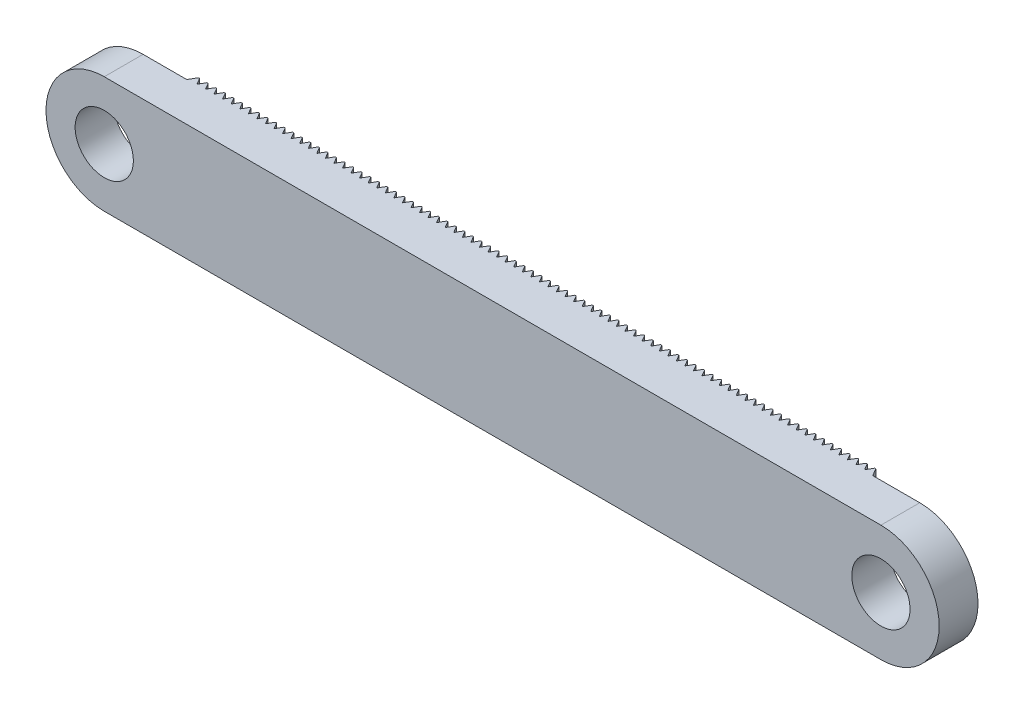
SolidWorks part; units mm, degrees
ref_plane "Front Plane" through (0, 0, 0) normal (0, 0, 1) x (1, 0, 0)
ref_plane "Top Plane" through (0, 0, 0) normal (0, 1, 0) x (1, 0, 0)
ref_plane "Right Plane" through (0, 0, 0) normal (1, 0, 0) x (0, 0, -1)
sketch "Sketch1" plane through (0, 0, 0) normal (0, 0, 1) x (1, 0, 0)
  line L0 (-20, 0) -> (20, 0) construction
  line L1 (-20, 3) -> (20, 3)
  line L2 (-20, -3) -> (20, -3)
  line L3 (0, 3) -> (0, -3) construction
  arc A0 (-20, 3) -> (-20, -3) centre (-20, 0) ccw
  arc A1 (20, -3) -> (20, 3) centre (20, 0) ccw
  circle A2 centre (-20, 0) radius 1.5
  circle A3 centre (20, 0) radius 1.5
  point P3 (0, 0)
  dimension "D1" = 3
  dimension "D2" = 40
  dimension "D3" = 6
extrude "Boss-Extrude1" add sketch "Sketch1" along normal blind 2
sketch "Sketch2" plane through (0, 0, 2) normal (0, 0, 1) x (1, 0, 0)
  circle A0 centre (0, 0) radius 1
  dimension "D1" = 2
extrude "Boss-Extrude2" [suppressed] add sketch "Sketch2" along normal blind 5
fillet "Fillet1" [suppressed] radius 0.25
sketch "Sketch5" plane through (0, 0, 0) normal (0, 1, 0) x (1, 0, 0)
  line L0 (-17.5306, 0.38) -> (-17.4694, 0.38)
  line L1 (-17.75, 0) -> (-17.5306, 0.38)
  line L2 (-17.4694, 0.38) -> (-17.25, 0)
  line L3 (20, 0) -> (-20, 0) construction
  line L4 (-17.25, 0) -> (-17.75, 0)
  line L5 (-17.3092, 0) -> (-17.0898, 0.38)
  line L6 (-17.0898, 0.38) -> (-17.0285, 0.38)
  line L7 (-17.0285, 0.38) -> (-16.8092, 0)
  line L8 (-16.8092, 0) -> (-17.3092, 0)
  line L9 (-16.8683, 0) -> (-16.6489, 0.38)
  line L10 (-16.6489, 0.38) -> (-16.5877, 0.38)
  line L11 (-16.5877, 0.38) -> (-16.3683, 0)
  line L12 (-16.3683, 0) -> (-16.8683, 0)
  line L13 (-16.4275, 0) -> (-16.2081, 0.38)
  line L14 (-16.2081, 0.38) -> (-16.1469, 0.38)
  line L15 (-16.1469, 0.38) -> (-15.9275, 0)
  line L16 (-15.9275, 0) -> (-16.4275, 0)
  line L17 (-15.9866, 0) -> (-15.7672, 0.38)
  line L18 (-15.7672, 0.38) -> (-15.706, 0.38)
  line L19 (-15.706, 0.38) -> (-15.4866, 0)
  line L20 (-15.4866, 0) -> (-15.9866, 0)
  line L21 (-15.5458, 0) -> (-15.3264, 0.38)
  line L22 (-15.3264, 0.38) -> (-15.2652, 0.38)
  line L23 (-15.2652, 0.38) -> (-15.0458, 0)
  line L24 (-15.0458, 0) -> (-15.5458, 0)
  line L25 (-15.1049, 0) -> (-14.8855, 0.38)
  line L26 (-14.8855, 0.38) -> (-14.8243, 0.38)
  line L27 (-14.8243, 0.38) -> (-14.6049, 0)
  line L28 (-14.6049, 0) -> (-15.1049, 0)
  line L29 (-14.6641, 0) -> (-14.4447, 0.38)
  line L30 (-14.4447, 0.38) -> (-14.3835, 0.38)
  line L31 (-14.3835, 0.38) -> (-14.1641, 0)
  line L32 (-14.1641, 0) -> (-14.6641, 0)
  line L33 (-14.2232, 0) -> (-14.0038, 0.38)
  line L34 (-14.0038, 0.38) -> (-13.9426, 0.38)
  line L35 (-13.9426, 0.38) -> (-13.7232, 0)
  line L36 (-13.7232, 0) -> (-14.2232, 0)
  line L37 (-13.7824, 0) -> (-13.563, 0.38)
  line L38 (-13.563, 0.38) -> (-13.5018, 0.38)
  line L39 (-13.5018, 0.38) -> (-13.2824, 0)
  line L40 (-13.2824, 0) -> (-13.7824, 0)
  line L41 (-13.3416, 0) -> (-13.1222, 0.38)
  line L42 (-13.1222, 0.38) -> (-13.0609, 0.38)
  line L43 (-13.0609, 0.38) -> (-12.8416, 0)
  line L44 (-12.8416, 0) -> (-13.3416, 0)
  line L45 (-12.9007, 0) -> (-12.6813, 0.38)
  line L46 (-12.6813, 0.38) -> (-12.6201, 0.38)
  line L47 (-12.6201, 0.38) -> (-12.4007, 0)
  line L48 (-12.4007, 0) -> (-12.9007, 0)
  line L49 (-12.4599, 0) -> (-12.2405, 0.38)
  line L50 (-12.2405, 0.38) -> (-12.1793, 0.38)
  line L51 (-12.1793, 0.38) -> (-11.9599, 0)
  line L52 (-11.9599, 0) -> (-12.4599, 0)
  line L53 (-12.019, 0) -> (-11.7996, 0.38)
  line L54 (-11.7996, 0.38) -> (-11.7384, 0.38)
  line L55 (-11.7384, 0.38) -> (-11.519, 0)
  line L56 (-11.519, 0) -> (-12.019, 0)
  line L57 (-11.5782, 0) -> (-11.3588, 0.38)
  line L58 (-11.3588, 0.38) -> (-11.2976, 0.38)
  line L59 (-11.2976, 0.38) -> (-11.0782, 0)
  line L60 (-11.0782, 0) -> (-11.5782, 0)
  line L61 (-11.1373, 0) -> (-10.9179, 0.38)
  line L62 (-10.9179, 0.38) -> (-10.8567, 0.38)
  line L63 (-10.8567, 0.38) -> (-10.6373, 0)
  line L64 (-10.6373, 0) -> (-11.1373, 0)
  line L65 (-10.6965, 0) -> (-10.4771, 0.38)
  line L66 (-10.4771, 0.38) -> (-10.4159, 0.38)
  line L67 (-10.4159, 0.38) -> (-10.1965, 0)
  line L68 (-10.1965, 0) -> (-10.6965, 0)
  line L69 (-10.2556, 0) -> (-10.0362, 0.38)
  line L70 (-10.0362, 0.38) -> (-9.975, 0.38)
  line L71 (-9.975, 0.38) -> (-9.7556, 0)
  line L72 (-9.7556, 0) -> (-10.2556, 0)
  line L73 (-9.8148, 0) -> (-9.5954, 0.38)
  line L74 (-9.5954, 0.38) -> (-9.5342, 0.38)
  line L75 (-9.5342, 0.38) -> (-9.3148, 0)
  line L76 (-9.3148, 0) -> (-9.8148, 0)
  line L77 (-9.374, 0) -> (-9.1546, 0.38)
  line L78 (-9.1546, 0.38) -> (-9.0933, 0.38)
  line L79 (-9.0933, 0.38) -> (-8.874, 0)
  line L80 (-8.874, 0) -> (-9.374, 0)
  line L81 (-8.9331, 0) -> (-8.7137, 0.38)
  line L82 (-8.7137, 0.38) -> (-8.6525, 0.38)
  line L83 (-8.6525, 0.38) -> (-8.4331, 0)
  line L84 (-8.4331, 0) -> (-8.9331, 0)
  line L85 (-8.4923, 0) -> (-8.2729, 0.38)
  line L86 (-8.2729, 0.38) -> (-8.2117, 0.38)
  line L87 (-8.2117, 0.38) -> (-7.9923, 0)
  line L88 (-7.9923, 0) -> (-8.4923, 0)
  line L89 (-8.0514, 0) -> (-7.832, 0.38)
  line L90 (-7.832, 0.38) -> (-7.7708, 0.38)
  line L91 (-7.7708, 0.38) -> (-7.5514, 0)
  line L92 (-7.5514, 0) -> (-8.0514, 0)
  line L93 (-7.6106, 0) -> (-7.3912, 0.38)
  line L94 (-7.3912, 0.38) -> (-7.33, 0.38)
  line L95 (-7.33, 0.38) -> (-7.1106, 0)
  line L96 (-7.1106, 0) -> (-7.6106, 0)
  line L97 (-7.1697, 0) -> (-6.9503, 0.38)
  line L98 (-6.9503, 0.38) -> (-6.8891, 0.38)
  line L99 (-6.8891, 0.38) -> (-6.6697, 0)
  line L100 (-6.6697, 0) -> (-7.1697, 0)
  line L101 (-6.7289, 0) -> (-6.5095, 0.38)
  line L102 (-6.5095, 0.38) -> (-6.4483, 0.38)
  line L103 (-6.4483, 0.38) -> (-6.2289, 0)
  line L104 (-6.2289, 0) -> (-6.7289, 0)
  line L105 (-6.288, 0) -> (-6.0686, 0.38)
  line L106 (-6.0686, 0.38) -> (-6.0074, 0.38)
  line L107 (-6.0074, 0.38) -> (-5.788, 0)
  line L108 (-5.788, 0) -> (-6.288, 0)
  line L109 (-5.8472, 0) -> (-5.6278, 0.38)
  line L110 (-5.6278, 0.38) -> (-5.5666, 0.38)
  line L111 (-5.5666, 0.38) -> (-5.3472, 0)
  line L112 (-5.3472, 0) -> (-5.8472, 0)
  line L113 (-5.4063, 0) -> (-5.187, 0.38)
  line L114 (-5.187, 0.38) -> (-5.1257, 0.38)
  line L115 (-5.1257, 0.38) -> (-4.9063, 0)
  line L116 (-4.9063, 0) -> (-5.4063, 0)
  line L117 (-4.9655, 0) -> (-4.7461, 0.38)
  line L118 (-4.7461, 0.38) -> (-4.6849, 0.38)
  line L119 (-4.6849, 0.38) -> (-4.4655, 0)
  line L120 (-4.4655, 0) -> (-4.9655, 0)
  line L121 (-4.5247, 0) -> (-4.3053, 0.38)
  line L122 (-4.3053, 0.38) -> (-4.2441, 0.38)
  line L123 (-4.2441, 0.38) -> (-4.0247, 0)
  line L124 (-4.0247, 0) -> (-4.5247, 0)
  line L125 (-4.0838, 0) -> (-3.8644, 0.38)
  line L126 (-3.8644, 0.38) -> (-3.8032, 0.38)
  line L127 (-3.8032, 0.38) -> (-3.5838, 0)
  line L128 (-3.5838, 0) -> (-4.0838, 0)
  line L129 (-3.643, 0) -> (-3.4236, 0.38)
  line L130 (-3.4236, 0.38) -> (-3.3624, 0.38)
  line L131 (-3.3624, 0.38) -> (-3.143, 0)
  line L132 (-3.143, 0) -> (-3.643, 0)
  line L133 (-3.2021, 0) -> (-2.9827, 0.38)
  line L134 (-2.9827, 0.38) -> (-2.9215, 0.38)
  line L135 (-2.9215, 0.38) -> (-2.7021, 0)
  line L136 (-2.7021, 0) -> (-3.2021, 0)
  line L137 (-2.7613, 0) -> (-2.5419, 0.38)
  line L138 (-2.5419, 0.38) -> (-2.4807, 0.38)
  line L139 (-2.4807, 0.38) -> (-2.2613, 0)
  line L140 (-2.2613, 0) -> (-2.7613, 0)
  line L141 (-2.3204, 0) -> (-2.101, 0.38)
  line L142 (-2.101, 0.38) -> (-2.0398, 0.38)
  line L143 (-2.0398, 0.38) -> (-1.8204, 0)
  line L144 (-1.8204, 0) -> (-2.3204, 0)
  line L145 (-1.8796, 0) -> (-1.6602, 0.38)
  line L146 (-1.6602, 0.38) -> (-1.599, 0.38)
  line L147 (-1.599, 0.38) -> (-1.3796, 0)
  line L148 (-1.3796, 0) -> (-1.8796, 0)
  line L149 (-1.4387, 0) -> (-1.2194, 0.38)
  line L150 (-1.2194, 0.38) -> (-1.1581, 0.38)
  line L151 (-1.1581, 0.38) -> (-0.9387, 0)
  line L152 (-0.9387, 0) -> (-1.4387, 0)
  line L153 (-0.9979, 0) -> (-0.7785, 0.38)
  line L154 (-0.7785, 0.38) -> (-0.7173, 0.38)
  line L155 (-0.7173, 0.38) -> (-0.4979, 0)
  line L156 (-0.4979, 0) -> (-0.9979, 0)
  line L157 (-0.5571, 0) -> (-0.3377, 0.38)
  line L158 (-0.3377, 0.38) -> (-0.2765, 0.38)
  line L159 (-0.2765, 0.38) -> (-0.0571, 0)
  line L160 (-0.0571, 0) -> (-0.5571, 0)
  line L161 (-0.1162, 0) -> (0.1032, 0.38)
  line L162 (0.1032, 0.38) -> (0.1644, 0.38)
  line L163 (0.1644, 0.38) -> (0.3838, 0)
  line L164 (0.3838, 0) -> (-0.1162, 0)
  line L165 (0.3246, 0) -> (0.544, 0.38)
  line L166 (0.544, 0.38) -> (0.6052, 0.38)
  line L167 (0.6052, 0.38) -> (0.8246, 0)
  line L168 (0.8246, 0) -> (0.3246, 0)
  line L169 (0.7655, 0) -> (0.9849, 0.38)
  line L170 (0.9849, 0.38) -> (1.0461, 0.38)
  line L171 (1.0461, 0.38) -> (1.2655, 0)
  line L172 (1.2655, 0) -> (0.7655, 0)
  line L173 (1.2063, 0) -> (1.4257, 0.38)
  line L174 (1.4257, 0.38) -> (1.4869, 0.38)
  line L175 (1.4869, 0.38) -> (1.7063, 0)
  line L176 (1.7063, 0) -> (1.2063, 0)
  line L177 (1.6472, 0) -> (1.8666, 0.38)
  line L178 (1.8666, 0.38) -> (1.9278, 0.38)
  line L179 (1.9278, 0.38) -> (2.1472, 0)
  line L180 (2.1472, 0) -> (1.6472, 0)
  line L181 (2.088, 0) -> (2.3074, 0.38)
  line L182 (2.3074, 0.38) -> (2.3686, 0.38)
  line L183 (2.3686, 0.38) -> (2.588, 0)
  line L184 (2.588, 0) -> (2.088, 0)
  line L185 (2.5289, 0) -> (2.7482, 0.38)
  line L186 (2.7482, 0.38) -> (2.8095, 0.38)
  line L187 (2.8095, 0.38) -> (3.0289, 0)
  line L188 (3.0289, 0) -> (2.5289, 0)
  line L189 (2.9697, 0) -> (3.1891, 0.38)
  line L190 (3.1891, 0.38) -> (3.2503, 0.38)
  line L191 (3.2503, 0.38) -> (3.4697, 0)
  line L192 (3.4697, 0) -> (2.9697, 0)
  line L193 (3.4105, 0) -> (3.6299, 0.38)
  line L194 (3.6299, 0.38) -> (3.6912, 0.38)
  line L195 (3.6912, 0.38) -> (3.9105, 0)
  line L196 (3.9105, 0) -> (3.4105, 0)
  line L197 (3.8514, 0) -> (4.0708, 0.38)
  line L198 (4.0708, 0.38) -> (4.132, 0.38)
  line L199 (4.132, 0.38) -> (4.3514, 0)
  line L200 (4.3514, 0) -> (3.8514, 0)
  line L201 (4.2922, 0) -> (4.5116, 0.38)
  line L202 (4.5116, 0.38) -> (4.5728, 0.38)
  line L203 (4.5728, 0.38) -> (4.7922, 0)
  line L204 (4.7922, 0) -> (4.2922, 0)
  line L205 (4.7331, 0) -> (4.9525, 0.38)
  line L206 (4.9525, 0.38) -> (5.0137, 0.38)
  line L207 (5.0137, 0.38) -> (5.2331, 0)
  line L208 (5.2331, 0) -> (4.7331, 0)
  line L209 (5.1739, 0) -> (5.3933, 0.38)
  line L210 (5.3933, 0.38) -> (5.4545, 0.38)
  line L211 (5.4545, 0.38) -> (5.6739, 0)
  line L212 (5.6739, 0) -> (5.1739, 0)
  line L213 (5.6148, 0) -> (5.8342, 0.38)
  line L214 (5.8342, 0.38) -> (5.8954, 0.38)
  line L215 (5.8954, 0.38) -> (6.1148, 0)
  line L216 (6.1148, 0) -> (5.6148, 0)
  line L217 (6.0556, 0) -> (6.275, 0.38)
  line L218 (6.275, 0.38) -> (6.3362, 0.38)
  line L219 (6.3362, 0.38) -> (6.5556, 0)
  line L220 (6.5556, 0) -> (6.0556, 0)
  line L221 (6.4965, 0) -> (6.7158, 0.38)
  line L222 (6.7158, 0.38) -> (6.7771, 0.38)
  line L223 (6.7771, 0.38) -> (6.9965, 0)
  line L224 (6.9965, 0) -> (6.4965, 0)
  line L225 (6.9373, 0) -> (7.1567, 0.38)
  line L226 (7.1567, 0.38) -> (7.2179, 0.38)
  line L227 (7.2179, 0.38) -> (7.4373, 0)
  line L228 (7.4373, 0) -> (6.9373, 0)
  line L229 (7.3781, 0) -> (7.5975, 0.38)
  line L230 (7.5975, 0.38) -> (7.6588, 0.38)
  line L231 (7.6588, 0.38) -> (7.8781, 0)
  line L232 (7.8781, 0) -> (7.3781, 0)
  line L233 (7.819, 0) -> (8.0384, 0.38)
  line L234 (8.0384, 0.38) -> (8.0996, 0.38)
  line L235 (8.0996, 0.38) -> (8.319, 0)
  line L236 (8.319, 0) -> (7.819, 0)
  line L237 (8.2598, 0) -> (8.4792, 0.38)
  line L238 (8.4792, 0.38) -> (8.5404, 0.38)
  line L239 (8.5404, 0.38) -> (8.7598, 0)
  line L240 (8.7598, 0) -> (8.2598, 0)
  line L241 (8.7007, 0) -> (8.9201, 0.38)
  line L242 (8.9201, 0.38) -> (8.9813, 0.38)
  line L243 (8.9813, 0.38) -> (9.2007, 0)
  line L244 (9.2007, 0) -> (8.7007, 0)
  line L245 (9.1415, 0) -> (9.3609, 0.38)
  line L246 (9.3609, 0.38) -> (9.4221, 0.38)
  line L247 (9.4221, 0.38) -> (9.6415, 0)
  line L248 (9.6415, 0) -> (9.1415, 0)
  line L249 (9.5824, 0) -> (9.8018, 0.38)
  line L250 (9.8018, 0.38) -> (9.863, 0.38)
  line L251 (9.863, 0.38) -> (10.0824, 0)
  line L252 (10.0824, 0) -> (9.5824, 0)
  line L253 (10.0232, 0) -> (10.2426, 0.38)
  line L254 (10.2426, 0.38) -> (10.3038, 0.38)
  line L255 (10.3038, 0.38) -> (10.5232, 0)
  line L256 (10.5232, 0) -> (10.0232, 0)
  line L257 (10.4641, 0) -> (10.6835, 0.38)
  line L258 (10.6835, 0.38) -> (10.7447, 0.38)
  line L259 (10.7447, 0.38) -> (10.9641, 0)
  line L260 (10.9641, 0) -> (10.4641, 0)
  line L261 (10.9049, 0) -> (11.1243, 0.38)
  line L262 (11.1243, 0.38) -> (11.1855, 0.38)
  line L263 (11.1855, 0.38) -> (11.4049, 0)
  line L264 (11.4049, 0) -> (10.9049, 0)
  line L265 (11.3457, 0) -> (11.5651, 0.38)
  line L266 (11.5651, 0.38) -> (11.6264, 0.38)
  line L267 (11.6264, 0.38) -> (11.8457, 0)
  line L268 (11.8457, 0) -> (11.3457, 0)
  line L269 (11.7866, 0) -> (12.006, 0.38)
  line L270 (12.006, 0.38) -> (12.0672, 0.38)
  line L271 (12.0672, 0.38) -> (12.2866, 0)
  line L272 (12.2866, 0) -> (11.7866, 0)
  line L273 (12.2274, 0) -> (12.4468, 0.38)
  line L274 (12.4468, 0.38) -> (12.508, 0.38)
  line L275 (12.508, 0.38) -> (12.7274, 0)
  line L276 (12.7274, 0) -> (12.2274, 0)
  line L277 (12.6683, 0) -> (12.8877, 0.38)
  line L278 (12.8877, 0.38) -> (12.9489, 0.38)
  line L279 (12.9489, 0.38) -> (13.1683, 0)
  line L280 (13.1683, 0) -> (12.6683, 0)
  line L281 (13.1091, 0) -> (13.3285, 0.38)
  line L282 (13.3285, 0.38) -> (13.3897, 0.38)
  line L283 (13.3897, 0.38) -> (13.6091, 0)
  line L284 (13.6091, 0) -> (13.1091, 0)
  line L285 (13.55, 0) -> (13.7694, 0.38)
  line L286 (13.7694, 0.38) -> (13.8306, 0.38)
  line L287 (13.8306, 0.38) -> (14.05, 0)
  line L288 (14.05, 0) -> (13.55, 0)
  line L289 (13.9908, 0) -> (14.2102, 0.38)
  line L290 (14.2102, 0.38) -> (14.2714, 0.38)
  line L291 (14.2714, 0.38) -> (14.4908, 0)
  line L292 (14.4908, 0) -> (13.9908, 0)
  line L293 (14.4317, 0) -> (14.6511, 0.38)
  line L294 (14.6511, 0.38) -> (14.7123, 0.38)
  line L295 (14.7123, 0.38) -> (14.9317, 0)
  line L296 (14.9317, 0) -> (14.4317, 0)
  line L297 (14.8725, 0) -> (15.0919, 0.38)
  line L298 (15.0919, 0.38) -> (15.1531, 0.38)
  line L299 (15.1531, 0.38) -> (15.3725, 0)
  line L300 (15.3725, 0) -> (14.8725, 0)
  line L301 (15.3134, 0) -> (15.5327, 0.38)
  line L302 (15.5327, 0.38) -> (15.594, 0.38)
  line L303 (15.594, 0.38) -> (15.8134, 0)
  line L304 (15.8134, 0) -> (15.3134, 0)
  line L305 (15.7542, 0) -> (15.9736, 0.38)
  line L306 (15.9736, 0.38) -> (16.0348, 0.38)
  line L307 (16.0348, 0.38) -> (16.2542, 0)
  line L308 (16.2542, 0) -> (15.7542, 0)
  line L309 (16.195, 0) -> (16.4144, 0.38)
  line L310 (16.4144, 0.38) -> (16.4756, 0.38)
  line L311 (16.4756, 0.38) -> (16.695, 0)
  line L312 (16.695, 0) -> (16.195, 0)
  line L313 (16.6359, 0) -> (16.8553, 0.38)
  line L314 (16.8553, 0.38) -> (16.9165, 0.38)
  line L315 (16.9165, 0.38) -> (17.1359, 0)
  line L316 (17.1359, 0) -> (16.6359, 0)
  line L317 (17.0767, 0) -> (17.2961, 0.38)
  line L318 (17.2961, 0.38) -> (17.3573, 0.38)
  line L319 (17.3573, 0.38) -> (17.5767, 0)
  line L320 (17.5767, 0) -> (17.0767, 0)
  line L365 (-20, -2) -> (-20, 0) construction
  line L366 (21.926, 0) -> (22.1454, 0.38) [skipped]
  line L367 (22.1454, 0.38) -> (22.2066, 0.38) [skipped]
  line L368 (22.2066, 0.38) -> (22.426, 0) [skipped]
  line L369 (22.426, 0) -> (21.926, 0) [skipped]
  line L370 (21.4852, 0) -> (21.7046, 0.38) [skipped]
  line L371 (21.7046, 0.38) -> (21.7658, 0.38) [skipped]
  line L372 (21.7658, 0.38) -> (21.9852, 0) [skipped]
  line L373 (21.9852, 0) -> (21.4852, 0) [skipped]
  line L374 (21.0443, 0) -> (21.2637, 0.38) [skipped]
  line L375 (21.2637, 0.38) -> (21.3249, 0.38) [skipped]
  line L376 (21.3249, 0.38) -> (21.5443, 0) [skipped]
  line L377 (21.5443, 0) -> (21.0443, 0) [skipped]
  line L378 (20.6035, 0) -> (20.8229, 0.38) [skipped]
  line L379 (20.8229, 0.38) -> (20.8841, 0.38) [skipped]
  line L380 (20.8841, 0.38) -> (21.1035, 0) [skipped]
  line L381 (21.1035, 0) -> (20.6035, 0) [skipped]
  line L382 (20.1626, 0) -> (20.382, 0.38) [skipped]
  line L383 (20.382, 0.38) -> (20.4432, 0.38) [skipped]
  line L384 (20.4432, 0.38) -> (20.6626, 0) [skipped]
  line L385 (20.6626, 0) -> (20.1626, 0) [skipped]
  line L386 (19.7218, 0) -> (19.9412, 0.38) [skipped]
  line L387 (19.9412, 0.38) -> (20.0024, 0.38) [skipped]
  line L388 (20.0024, 0.38) -> (20.2218, 0) [skipped]
  line L389 (20.2218, 0) -> (19.7218, 0) [skipped]
  line L390 (19.281, 0) -> (19.5003, 0.38) [skipped]
  line L391 (19.5003, 0.38) -> (19.5616, 0.38) [skipped]
  line L392 (19.5616, 0.38) -> (19.781, 0) [skipped]
  line L393 (19.781, 0) -> (19.281, 0) [skipped]
  line L394 (18.8401, 0) -> (19.0595, 0.38) [skipped]
  line L395 (19.0595, 0.38) -> (19.1207, 0.38) [skipped]
  line L396 (19.1207, 0.38) -> (19.3401, 0) [skipped]
  line L397 (19.3401, 0) -> (18.8401, 0) [skipped]
  line L398 (18.3993, 0) -> (18.6187, 0.38) [skipped]
  line L399 (18.6799, 0.38) -> (18.8993, 0) [skipped]
  line L400 (18.6187, 0.38) -> (18.6799, 0.38) [skipped]
  line L401 (17.9584, 0) -> (18.1778, 0.38) [skipped]
  line L402 (18.1778, 0.38) -> (18.239, 0.38) [skipped]
  line L403 (18.239, 0.38) -> (18.4584, 0) [skipped]
  line L404 (18.4584, 0) -> (17.9584, 0) [skipped]
  line L405 (17.5176, 0) -> (17.737, 0.38) [skipped]
  line L406 (17.737, 0.38) -> (17.7982, 0.38) [skipped]
  line L407 (17.7982, 0.38) -> (18.0176, 0) [skipped]
  line L408 (18.0176, 0) -> (17.5176, 0) [skipped]
  line L409 (18.8993, 0) -> (18.3993, 0) [skipped]
  point P3 (0, 0)
  dimension "D1" = 0.5
  dimension "D2" = 0.38
  dimension "D3" = 0.4388
  dimension "D5" = 2.25
  dimension "D4" = 91
extrude "Boss-Extrude6" add sketch "Sketch5" along normal mid plane 6 contours L4 L5 L2 L0 L1 | L8 L9 L7 L6 L5 L2 | L12 L13 L11 L10 L9 L7 | L16 L17 L15 L14 L13 L11 | L20 L21 L19 L18 L17 L15 | L24 L25 L23 L22 L21 L19 | L28 L29 L27 L26 L25 L23 | L32 L33 L31 L30 L29 L27 | L36 L37 L35 L34 L33 L31 | L40 L41 L39 L38 L37 L35 | L48 L49 L47 L46 L45 L43 | L56 L57 L55 L54 L53 L51 | L60 L61 L59 L58 L57 L55 | L64 L65 L63 L62 L61 L59 | L68 L69 L67 L66 L65 L63 | L72 L73 L71 L70 L69 L67 | L76 L77 L75 L74 L73 L71 | L80 L81 L79 L78 L77 L75 | L84 L85 L83 L82 L81 L79 | L88 L89 L87 L86 L85 L83 | L108 L109 L107 L106 L105 L103 | L112 L113 L111 L110 L109 L107 | L116 L117 L115 L114 L113 L111 | L120 L121 L119 L118 L117 L115 | L124 L125 L123 L122 L121 L119 | L128 L129 L127 L126 L125 L123 | L132 L133 L131 L130 L129 L127 | L136 L137 L135 L134 L133 L131 | L140 L141 L139 L138 L137 L135 | L144 L145 L143 L142 L141 L139 | L152 L153 L151 L150 L149 L147 | L164 L165 L163 L162 L161 L159 | L176 L177 L175 L174 L173 L171 | L180 L181 L179 L178 L177 L175 | L184 L185 L183 L182 L181 L179 | L188 L189 L187 L186 L185 L183 | L192 L193 L191 L190 L189 L187 | L196 L197 L195 L194 L193 L191 | L200 L201 L199 L198 L197 L195 | L220 L221 L219 L218 L217 L215 | L224 L225 L223 L222 L221 L219 | L228 L229 L227 L226 L225 L223 | L236 L237 L235 L234 L233 L231 | L240 L241 L239 L238 L237 L235 | L252 L253 L251 L250 L249 L247 | L256 L257 L255 L254 L253 L251 | L260 L261 L259 L258 L257 L255 | L268 L269 L267 L266 L265 L263 | L272 L273 L271 L270 L269 L267 | L276 L277 L275 L274 L273 L271 | L280 L281 L279 L278 L277 L275 | L284 L285 L283 L282 L281 L279 | L288 L289 L287 L286 L285 L283 | L292 L293 L291 L290 L289 L287 | L300 L301 L299 L298 L297 L295 | L304 L305 L303 L302 L301 L299 | L308 L309 L307 L306 L305 L303 | L312 L313 L311 L310 L309 L307 | L5 L4 L2 | L13 L12 L11 | L17 L16 L15 | L21 L20 L19 | L37 L36 L35 | L41 L40 L39 | L45 L44 L43 | L49 L48 L47 | L53 L52 L51 | L57 L56 L55 | L61 L60 L59 | L65 L64 L63 | L69 L68 L67 | L73 L72 L71 | L85 L84 L83 | L100 L101 L99 L98 L97 L95 | L113 L112 L111 | L129 L128 L127 | L137 L136 L135 | L141 L140 L139 | L177 L176 L175 | L181 L180 L179 | L185 L184 L183 | L189 L188 L187 | L192 L193 L191 L190 L189 L187 | L197 L196 L195 | L221 L220 L219 | L229 L228 L227 | L237 L236 L235 | L269 L268 L267 | L273 L272 L271 | L277 L276 L275 | L281 L280 L279 | L285 L284 L283 | L289 L288 L287 | L301 L300 L299 | L305 L304 L303 | L309 L308 L307 | L205 L206 L207 L208 | L209 L210 L211 L212 | L317 L318 L319 L320
